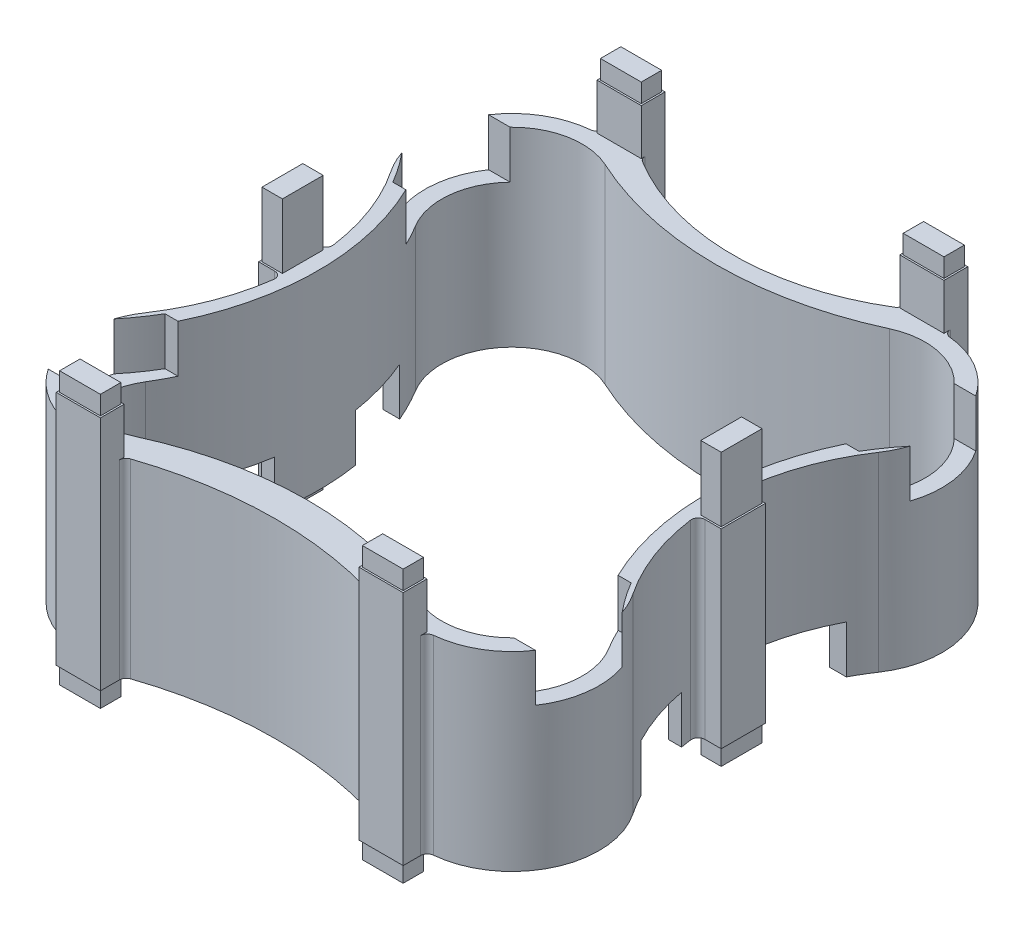
SolidWorks part; units mm, degrees
material "PA 类型 6"
ref_plane "前视基准面" through (0, 0, 0) normal (0, 0, 1) x (1, 0, 0)
ref_plane "上视基准面" through (0, 0, 0) normal (0, 1, 0) x (1, 0, 0)
ref_plane "右视基准面" through (0, 0, 0) normal (1, 0, 0) x (0, 0, -1)
sketch "参考面" plane through (0, 0, 0) normal (0, 1, 0) x (1, 0, 0)
  line L9 (-126.3139, 0) -> (116.7252, 0) construction
  line L10 (121.4406, 121.4406) -> (-121.4406, -121.4406) construction
  line L19 (-81.1154, 0) -> (102.0168, 0) construction
  line L20 (-108.2303, 108.2303) -> (124.7404, -124.7404) construction
  line L37 (0, 0) -> (86.2111, -62.636) construction
  line L56 (0, 63.4476) -> (0, -83.7805) construction
  line L92 (67.1165, -56.1685) -> (56.6027, -48.5298)
  line L94 (74.1596, -46.4745) -> (63.6458, -38.8359)
  line L111 (14.4084, 23.7665) -> (0, 9.3581)
  line L112 (21.4, 67.209) -> (28.6, 67.209)
  line L121 (4.0949, -56.1675) -> (4.0949, -53.2193)
  line L122 (-3.5956, -56.6668) -> (3.5956, -56.6668)
  line L123 (3.5956, -40.6902) -> (-3.5938, -40.6902)
  line L124 (4.0949, -41.1895) -> (4.0949, -44.1377)
  line L125 (-4.0949, -56.1675) -> (-4.0949, -53.2179)
  line L126 (-4.0949, -44.1363) -> (-4.0949, -41.1876)
  line L127 (-4.5418, -52.8684) -> (-4.4444, -52.8684)
  line L128 (-8.5359, -48.8743) -> (-8.5359, -48.4799)
  line L129 (8.5359, -48.8757) -> (8.5359, -48.4813)
  line L130 (4.4444, -52.8698) -> (4.5418, -52.8698)
  line L131 (4.5418, -44.4872) -> (4.4444, -44.4872)
  line L132 (-4.5418, -44.4858) -> (-4.4444, -44.4858)
  line L180 (-67.1165, 56.1685) -> (-56.6027, 48.5298)
  line L181 (-74.1596, 46.4745) -> (-63.6458, 38.8359)
  line L182 (-74.1596, -46.4745) -> (-63.6458, -38.8359)
  line L183 (-67.1165, -56.1685) -> (-56.6027, -48.5298)
  line L194 (-18.9731, -62.4083) -> (18.9712, -62.4083) construction
  line L200 (-11.2634, 52.145) -> (-6.2707, 52.145) construction
  line L201 (-11.2634, 50.8469) -> (-6.2707, 50.8469)
  line L202 (-11.2634, 53.4431) -> (-6.2707, 53.4431)
  line L206 (5.7117, 52.145) -> (0.719, 52.145) construction
  line L207 (5.7117, 53.4431) -> (0.719, 53.4431)
  line L208 (5.7117, 50.8469) -> (0.719, 50.8469)
  line L209 (74.1596, 46.4745) -> (63.6458, 38.8359)
  line L210 (43.9796, 31.9531) -> (60.1362, 43.6915) construction
  line L211 (67.1165, 56.1685) -> (56.6027, 48.5298)
  line L213 (-23.7665, 14.4084) -> (-9.3581, 0)
  line L214 (-58.8004, 0) -> (57.5251, 0) construction
  line L215 (-23.7665, -14.4084) -> (-9.3581, 0)
  line L241 (20.9, 49.291) -> (20.9, 66.709)
  line L242 (21.4, 48.791) -> (28.6, 48.791)
  line L243 (-14.4084, 23.7665) -> (0, 9.3581)
  line L244 (20.9, 58) -> (35.2287, 58) construction
  line L245 (25, 67.209) -> (25, 48.791) construction
  line L246 (29.1, 66.709) -> (29.1, 49.291)
  line L247 (23.7665, -14.4084) -> (9.3581, 0)
  line L248 (23.7665, 14.4084) -> (9.3581, 0)
  line L249 (-14.4084, -23.7665) -> (0, -9.3581)
  line L250 (14.4084, -23.7665) -> (0, -9.3581)
  line L255 (25.5, -41.5) -> (19, -41.5)
  line L256 (-25.5, 41.5) -> (-19, 41.5)
  line L257 (-25.5, 41.5) -> (-25.5, 38)
  line L258 (-25.5, 38) -> (-19, 38)
  line L259 (-19, 41.5) -> (-19, 38)
  line L260 (-34, 3.25) -> (-30.5, 3.25)
  line L261 (-34, 3.25) -> (-34, -3.25)
  line L262 (-34, -3.25) -> (-30.5, -3.25)
  line L263 (-30.5, 3.25) -> (-30.5, -3.25)
  line L264 (-25.5, -38) -> (-19, -38)
  line L265 (-25.5, -38) -> (-25.5, -41.5)
  line L266 (-25.5, -41.5) -> (-19, -41.5)
  line L267 (-19, -38) -> (-19, -41.5)
  line L268 (19, -38) -> (19, -41.5)
  line L269 (25.5, -38) -> (19, -38)
  line L270 (25.5, -38) -> (25.5, -41.5)
  line L271 (34, -3.25) -> (30.5, -3.25)
  line L272 (30.5, 3.25) -> (30.5, -3.25)
  line L273 (34, 3.25) -> (30.5, 3.25)
  line L274 (34, 3.25) -> (34, -3.25)
  line L275 (25.5, 38) -> (19, 38)
  line L276 (19, 41.5) -> (19, 38)
  line L277 (25.5, 41.5) -> (25.5, 38)
  line L278 (25.5, 41.5) -> (19, 41.5)
  circle A40 centre (9.9853, 9.9853) radius 1.0734
  circle A65 centre (12.7313, 12.7313) radius 1.0734
  circle A66 centre (15.2276, 15.2276) radius 1.5477
  circle A67 centre (-15.2276, 15.2276) radius 1.5477
  circle A68 centre (-12.7313, 12.7313) radius 1.0734
  circle A69 centre (-9.9853, 9.9853) radius 1.0734
  circle A70 centre (-9.9853, -9.9853) radius 1.0734
  circle A71 centre (-12.7313, -12.7313) radius 1.0734
  circle A72 centre (-15.2276, -15.2276) radius 1.5477
  circle A82 centre (15.2276, -15.2276) radius 1.5477
  circle A83 centre (12.7313, -12.7313) radius 1.0734
  circle A84 centre (9.9853, -9.9853) radius 1.0734
  circle A85 centre (27.9589, -27.9589) radius 3.1454
  circle A86 centre (-27.9589, -27.9589) radius 3.1454
  circle A101 centre (-27.9589, 27.9589) radius 3.1454
  circle A102 centre (27.9589, 27.9589) radius 3.1454
  circle A104 centre (43.9796, -31.9531) radius 1.5477
  circle A105 centre (60.1362, -43.6915) radius 1.5477
  circle A106 centre (-60.1362, -43.6915) radius 1.5477
  circle A113 centre (-23.2458, 52.145) radius 1.2981
  circle A114 centre (-43.9796, -31.9531) radius 1.5477
  circle A115 centre (60.1362, 43.6915) radius 1.5477
  circle A116 centre (43.9796, 31.9531) radius 1.5477
  circle A117 centre (-43.9796, 31.9531) radius 1.5477
  circle A118 centre (-60.1362, 43.6915) radius 1.5477
  arc A120 (67.1165, -56.1685) -> (74.1596, -46.4745) centre (70.638, -51.3215) ccw
  arc A121 (27.2174, -63.5024) -> (56.6027, -48.5298) centre (45.7245, -63.5024) cw
  arc A128 (-4.0949, -56.1675) -> (-3.5956, -56.6668) centre (-4.0949, -56.6668) ccw
  arc A129 (4.0949, -56.1675) -> (3.5956, -56.6668) centre (4.0949, -56.6668) cw
  arc A130 (4.0949, -41.1895) -> (3.5956, -40.6902) centre (4.0949, -40.6902) ccw
  arc A131 (-4.0949, -41.1876) -> (-3.5938, -40.6902) centre (-4.0931, -40.6884) cw
  arc A132 (8.5359, -48.4813) -> (4.5418, -44.4872) centre (4.5418, -48.4813) ccw
  arc A133 (-4.5418, -44.4858) -> (-8.5359, -48.4799) centre (-4.5418, -48.4799) ccw
  arc A134 (-4.5418, -52.8684) -> (-8.5359, -48.8743) centre (-4.5418, -48.8743) cw
  arc A135 (8.5359, -48.8757) -> (4.5418, -52.8698) centre (4.5418, -48.8757) cw
  arc A136 (4.0949, -44.1377) -> (4.4444, -44.4872) centre (4.4444, -44.1377) ccw
  arc A137 (4.0949, -53.2193) -> (4.4444, -52.8698) centre (4.4444, -53.2193) cw
  arc A138 (-4.0949, -44.1363) -> (-4.4444, -44.4858) centre (-4.4444, -44.1363) cw
  arc A139 (-4.0949, -53.2179) -> (-4.4444, -52.8684) centre (-4.4444, -53.2179) ccw
  arc A165 (-11.2634, 50.8469) -> (-11.2634, 53.4431) centre (-11.2634, 52.145) cw
  arc A166 (-6.2707, 53.4431) -> (-6.2707, 50.8469) centre (-6.2707, 52.145) cw
  arc A169 (5.7117, 53.4431) -> (5.7117, 50.8469) centre (5.7117, 52.145) cw
  arc A170 (0.719, 50.8469) -> (0.719, 53.4431) centre (0.719, 52.145) cw
  circle A175 centre (0, -38.4435) radius 1.5477
  circle A176 centre (0, -58.9135) radius 1.5477
  arc A177 (67.1165, 56.1685) -> (74.1596, 46.4745) centre (70.638, 51.3215) cw
  arc A178 (63.6458, 38.8359) -> (63.6458, -38.8359) centre (91.8617, 0) ccw
  circle A179 centre (43.9796, -31.9531) radius 5.9912 construction
  arc A180 (35.3497, 58.9683) -> (56.6027, 48.5298) centre (48.7329, 59.3617) ccw
  arc A181 (-67.1165, 56.1685) -> (-74.1596, 46.4745) centre (-70.638, 51.3215) ccw
  arc A182 (-35.3497, 58.9683) -> (-56.6027, 48.5298) centre (-48.7329, 59.3617) cw
  arc A183 (-63.6458, 38.8359) -> (-63.6458, -38.8359) centre (-91.8617, 0) cw
  arc A184 (-67.1165, -56.1685) -> (-74.1596, -46.4745) centre (-70.638, -51.3215) cw
  arc A185 (-27.2174, -63.5024) -> (-56.6027, -48.5298) centre (-45.7245, -63.5024) ccw
  arc A190 (-23.7665, 14.4084) -> (-29.7764, 19.3723) centre (-52.8107, -14.6358) ccw
  arc A191 (-23.7665, -14.4084) -> (-29.7764, -19.3723) centre (-52.8107, 14.6358) cw
  arc A192 (-29.7764, -19.3723) -> (-29.7764, 19.3723) centre (-91.8617, 0) ccw
  circle A202 centre (25, 69.659) radius 1.05
  arc A203 (20.9, 66.709) -> (21.4, 67.209) centre (20.9, 67.209) cw
  arc A204 (20.9, 49.291) -> (21.4, 48.791) centre (20.9, 48.791) ccw
  circle A205 centre (25, 46.341) radius 1.05
  arc A206 (29.1, 66.709) -> (28.6, 67.209) centre (29.1, 67.209) ccw
  arc A207 (29.1, 49.291) -> (28.6, 48.791) centre (29.1, 48.791) cw
  arc A208 (-14.4084, 23.7665) -> (-19.3723, 29.7764) centre (14.6358, 52.8107) cw
  arc A209 (-19.3723, 29.7764) -> (19.3723, 29.7764) centre (0, 91.8617) ccw
  arc A210 (14.4084, 23.7665) -> (19.3723, 29.7764) centre (-14.6358, 52.8107) ccw
  arc A211 (23.7665, 14.4084) -> (29.7764, 19.3723) centre (52.8107, -14.6358) cw
  arc A212 (29.7764, 19.3723) -> (29.7764, -19.3723) centre (91.8617, 0) ccw
  arc A213 (23.7665, -14.4084) -> (29.7764, -19.3723) centre (52.8107, 14.6358) ccw
  arc A214 (14.4084, -23.7665) -> (19.3723, -29.7764) centre (-14.6358, -52.8107) cw
  arc A215 (19.3723, -29.7764) -> (-19.3723, -29.7764) centre (0, -91.8617) ccw
  arc A216 (-14.4084, -23.7665) -> (-19.3723, -29.7764) centre (14.6358, -52.8107) ccw
  point P77 (0, 0)
  point P112 (-8.7671, 52.145)
  point P168 (3.2153, 52.145)
  point P443 (0, 0)
  dimension "D1" = 4
  dimension "D3" = 58
  dimension "D5" = 8.2
  dimension "D2" = 0.5
  dimension "D4" = 2.45
  dimension "D6" = 7.2
  dimension "D7" = 25
  dimension "D8" = 19
  dimension "D9" = 30.5
  dimension "D14" = 6.5
  dimension "D15" = 3.5
  dimension "D16" = 38
  dimension "D17" = 38
sketch "草图2" plane through (0, 0, 0) normal (0, 1, 0) x (1, 0, 0)
  line L1 (-61.3007, 0) -> (77.257, 0) construction
  line L8 (-30.5, 3.25) -> (-34, 3.25)
  line L9 (-34, 3.25) -> (-34, -3.25)
  line L31 (-34, -3.25) -> (-30.5, -3.25)
  line L33 (-25.5, 38) -> (-25.5, 41.5)
  line L56 (-25.5, 41.5) -> (-19, 41.5)
  line L57 (-19, 41.5) -> (-19, 38)
  line L58 (-25.5, -38) -> (-25.5, -41.5)
  line L59 (-25.5, -41.5) -> (-19, -41.5)
  line L60 (-19, -41.5) -> (-19, -38)
  line L61 (19, -41.5) -> (19, -38)
  line L62 (25.5, -41.5) -> (19, -41.5)
  line L63 (25.5, -38) -> (25.5, -41.5)
  line L64 (19, 41.5) -> (19, 38)
  line L65 (25.5, 41.5) -> (19, 41.5)
  line L66 (25.5, 38) -> (25.5, 41.5)
  line L67 (34, -3.25) -> (30.5, -3.25)
  line L68 (34, 3.25) -> (34, -3.25)
  line L69 (30.5, 3.25) -> (34, 3.25)
  line L74 (-126.3139, 0) -> (116.7252, 0) construction
  line L75 (0, 68.5797) -> (0, -68.5797) construction
  line L76 (0, 63.4476) -> (0, -83.7805) construction
  line L77 (-108.2303, 108.2303) -> (124.7404, -124.7404) construction
  arc A49 (-25.5, 38) -> (-35.8347, 18.0724) centre (-25.2016, 25.2016) ccw
  arc A52 (-20.8758, 34.5817) -> (-34.0392, 19.854) centre (-25.2016, 25.2016) ccw
  arc A53 (-34.0392, -19.854) -> (-34.0392, 19.854) centre (-66.8509, 0) ccw
  arc A55 (-35.8347, -18.0724) -> (-30.5, -3.25) centre (-62.7894, 0) ccw
  arc A56 (-25.5, -38) -> (-35.8347, -18.0724) centre (-25.2016, -25.2016) cw
  arc A57 (-20.8758, -34.5817) -> (-34.0392, -19.854) centre (-25.2016, -25.2016) cw
  arc A59 (-30.5, 3.25) -> (-35.8347, 18.0724) centre (-62.7894, 0) ccw
  arc A62 (30.5, 3.25) -> (35.8347, 18.0724) centre (62.7894, 0) cw
  arc A65 (20.8758, -34.5817) -> (34.0392, -19.854) centre (25.2016, -25.2016) ccw
  arc A66 (25.5, -38) -> (35.8347, -18.0724) centre (25.2016, -25.2016) ccw
  arc A69 (35.8347, -18.0724) -> (30.5, -3.25) centre (62.7894, 0) cw
  arc A70 (34.0392, -19.854) -> (34.0392, 19.854) centre (66.8509, 0) cw
  arc A71 (20.8758, 34.5817) -> (34.0392, 19.854) centre (25.2016, 25.2016) cw
  arc A72 (25.5, 38) -> (35.8347, 18.0724) centre (25.2016, 25.2016) cw
  arc A73 (-19, 38) -> (19, 38) centre (0, 67.9818) ccw
  arc A74 (-20.8758, 34.5817) -> (20.8758, 34.5817) centre (0, 79.8492) ccw
  arc A75 (-19, -38) -> (19, -38) centre (0, -91.6977) cw
  arc A76 (-20.8758, -34.5817) -> (20.8758, -34.5817) centre (0, -79.8492) cw
  point P33 (-28.5, 0)
  point P34 (28.5, 0)
  point P37 (0, 30)
  point P38 (0, -30)
  point P44 (-36.5661, 31.0954)
  point P54 (0, 32.4866)
  dimension "D1" = 2
  dimension "D3" = 60
  dimension "D5" = 2.4866
  dimension "D2" = 57
  dimension "D4" = 48
extrude "主结构-28mm-铝柱补偿7mm" add sketch "草图2" against normal blind 28
sketch "草图9" plane through (0, 0, 0) normal (0, 1, 0) x (1, 0, 0)
  line L0 (-25.5, 41.5) -> (-19, 41.5)
  line L1 (-19, 41.5) -> (-19, 38)
  line L2 (-19, 38) -> (-25.5, 38)
  line L3 (-25.5, 38) -> (-25.5, 41.5)
  line L4 (-34, 3.25) -> (-30.5, 3.25)
  line L5 (-30.5, 3.25) -> (-30.5, -3.25)
  line L6 (-30.5, -3.25) -> (-34, -3.25)
  line L7 (-34, -3.25) -> (-34, 3.25)
  line L8 (-25.5, -38) -> (-19, -38)
  line L9 (-19, -38) -> (-19, -41.5)
  line L10 (-19, -41.5) -> (-25.5, -41.5)
  line L11 (-25.5, -41.5) -> (-25.5, -38)
  line L12 (0, 0) -> (0, 49.4307) construction
  line L13 (25.5, -41.5) -> (25.5, -38)
  line L14 (19, -41.5) -> (25.5, -41.5)
  line L15 (19, -38) -> (19, -41.5)
  line L16 (25.5, -38) -> (19, -38)
  line L17 (34, -3.25) -> (34, 3.25)
  line L18 (30.5, -3.25) -> (34, -3.25)
  line L19 (30.5, 3.25) -> (30.5, -3.25)
  line L20 (34, 3.25) -> (30.5, 3.25)
  line L21 (25.5, 38) -> (25.5, 41.5)
  line L22 (19, 38) -> (25.5, 38)
  line L23 (19, 41.5) -> (19, 38)
  line L24 (25.5, 41.5) -> (19, 41.5)
  line M16 (-25.5, -38) -> (-25.5, -41.5)
  line M17 (-25.5, -41.5) -> (-19, -41.5)
  line M18 (-19, -41.5) -> (-19, -38)
  line M20 (19, -38) -> (19, -41.5)
  line M21 (19, -41.5) -> (25.5, -41.5)
  line M22 (25.5, -41.5) -> (25.5, -38)
  line M30 (25.5, 38) -> (25.5, 41.5)
  line M31 (25.5, 41.5) -> (19, 41.5)
  line M32 (19, 41.5) -> (19, 38)
  line M34 (-19, 38) -> (-19, 41.5)
  line M35 (-19, 41.5) -> (-25.5, 41.5)
  line M36 (-25.5, 41.5) -> (-25.5, 38)
extrude "上板支撑" add sketch "草图9" along normal blind 6.75 contours L2 M34 M35 M36 | L22 M32 M30 M31 | L8 M16 M17 M18 | L16 M22 M20 M21 region at (-22.25, 0, -39.75) region at (-22.25, 0, 39.75) region at (22.25, 0, 39.75) region at (22.25, 0, -39.75)
sketch "草图5" plane through (0, 0, 0) normal (0, 1, 0) x (1, 0, 0)
  line L0 (-68.648, 0) -> (77.219, 0) construction
  line L1 (-126.3139, 0) -> (116.7252, 0) construction
  line L2 (0, 57.3258) -> (0, -69.9488) construction
  line L3 (0, 63.4476) -> (0, -83.7805) construction
  line L4 (-34, 3.25) -> (-30.5, 3.25) construction
  line L5 (-33.75, 3) -> (-30.75, 3)
  line L6 (-33.75, 3) -> (-33.75, -3)
  line L7 (-33.75, -3) -> (-30.75, -3)
  line L8 (-30.75, 3) -> (-30.75, -3)
  line L9 (-34, 3.25) -> (-34, -3.25) construction
  line L10 (-19, -38) -> (-19, -41.5) construction
  line L11 (-25.25, -38.25) -> (-19.25, -38.25)
  line L12 (-25.25, -38.25) -> (-25.25, -41.25)
  line L13 (-25.25, -41.25) -> (-19.25, -41.25)
  line L14 (-19.25, -38.25) -> (-19.25, -41.25)
  line L15 (-25.5, -41.5) -> (-19, -41.5) construction
  line L16 (-25.25, 41.25) -> (-19.25, 41.25)
  line L17 (-19.25, 38.25) -> (-19.25, 41.25)
  line L18 (-25.25, 38.25) -> (-19.25, 38.25)
  line L19 (-25.25, 38.25) -> (-25.25, 41.25)
  line L20 (25.25, 38.25) -> (25.25, 41.25)
  line L21 (25.25, 38.25) -> (19.25, 38.25)
  line L22 (19.25, 38.25) -> (19.25, 41.25)
  line L23 (25.25, 41.25) -> (19.25, 41.25)
  line L24 (19.25, -38.25) -> (19.25, -41.25)
  line L25 (25.25, -41.25) -> (19.25, -41.25)
  line L26 (25.25, -38.25) -> (25.25, -41.25)
  line L27 (25.25, -38.25) -> (19.25, -38.25)
  line L28 (30.75, 3) -> (30.75, -3)
  line L29 (33.75, -3) -> (30.75, -3)
  line L30 (33.75, 3) -> (33.75, -3)
  line L31 (33.75, 3) -> (30.75, 3)
  dimension "D1" = 0.25
  dimension "D2" = 0.25
  dimension "D3" = 3
  dimension "D4" = 0.25
  dimension "D5" = 0.25
extrude "凸台-拉伸3" add sketch "草图5" along normal blind 9.5 contours L19 L18 L17 L16 | L20 L23 L22 L21 | L8 L5 L6 L7 | L26 L27 L24 L25 | L14 L11 L12 L13 | L30 L29 L28 L31 region at (-32.25, 0, 0) region at (-22.25, 0, 39.75) region at (-22.25, 0, -39.75) region at (22.25, 0, -39.75) region at (22.25, 0, 39.75)
sketch "草图6" plane through (0, -28, 0) normal (0, -1, 0) x (1, 0, 0)
  line L0 (-44.389, 0) -> (42.3877, 0) construction
  line L1 (0, 51.2716) -> (0, -51.2716) construction
  line L2 (-25.25, 41.25) -> (-19.25, 41.25)
  line L3 (-33.75, 3) -> (-30.75, 3)
  line L4 (-33.75, 3) -> (-33.75, -3)
  line L5 (-33.75, -3) -> (-30.75, -3)
  line L6 (-30.75, 3) -> (-30.75, -3)
  line L7 (-25.25, -38.25) -> (-19.25, -38.25)
  line L8 (-25.25, -38.25) -> (-25.25, -41.25)
  line L9 (-25.25, -41.25) -> (-19.25, -41.25)
  line L10 (-19.25, -38.25) -> (-19.25, -41.25)
  line L11 (-19.25, 38.25) -> (-19.25, 41.25)
  line L12 (-25.25, 38.25) -> (-19.25, 38.25)
  line L13 (-25.25, 38.25) -> (-25.25, 41.25)
  line L14 (25.25, 38.25) -> (25.25, 41.25)
  line L15 (25.25, 38.25) -> (19.25, 38.25)
  line L16 (19.25, 38.25) -> (19.25, 41.25)
  line L17 (19.25, -38.25) -> (19.25, -41.25)
  line L18 (25.25, -41.25) -> (19.25, -41.25)
  line L19 (25.25, -38.25) -> (25.25, -41.25)
  line L20 (25.25, -38.25) -> (19.25, -38.25)
  line L21 (30.75, 3) -> (30.75, -3)
  line L22 (33.75, -3) -> (30.75, -3)
  line L23 (33.75, 3) -> (33.75, -3)
  line L24 (33.75, 3) -> (30.75, 3)
  line L25 (25.25, 41.25) -> (19.25, 41.25)
  line L26 (-34, 3.25) -> (-30.5, 3.25) construction
  line L27 (-34, -3.25) -> (-34, 3.25) construction
  line L28 (-25.5, -41.5) -> (-25.5, -38) construction
  line L29 (-19, -41.5) -> (-25.5, -41.5) construction
  dimension "D1" = 0.25
  dimension "D2" = 0.25
  dimension "D3" = 0.25
  dimension "D4" = 0.25
  dimension "D5" = 3
extrude "凸台-拉伸4" add sketch "草图6" along normal blind 2.5
fillet "圆角1" radius 1 12 edges at (30.5, -14, -3.25) (25.5, -14, -38) (-19, -14, -38) (19, -14, -38) (-25.5, -14, -38) (-30.5, -14, -3.25) (19, -14, 38) (30.5, -14, 3.25) (25.5, -14, 38) (-19, -14, 38) (-25.5, -14, 38) (-30.5, -14, 3.25)
sketch "草图7" plane through (0, 0, 0) normal (0, 1, 0) x (1, 0, 0)
  line L0 (-43.0337, 0) -> (42.851, 0) construction
  line L1 (0, 36.718) -> (0, -44.8375) construction
  line L2 (0, 0) -> (-41.2356, -29.9594) construction
  line L3 (-34.2586, -16.7459) -> (-32.3492, -16.7459)
  line L4 (-35.8097, -32.3679) -> (-32.6409, -32.3679)
  line L5 (34.2586, -16.7459) -> (32.3492, -16.7459)
  line L6 (35.8097, -32.3679) -> (32.6409, -32.3679)
  line L8 (-34.2586, 16.7459) -> (-32.3492, 16.7459)
  line L9 (-35.8097, 32.3679) -> (-32.6409, 32.3679)
  line L10 (35.8097, 32.3679) -> (32.6409, 32.3679)
  line L11 (34.2586, 16.7459) -> (32.3492, 16.7459)
  arc A0 (-34.0392, -19.854) -> (-32.6409, -32.3679) centre (-25.2016, -25.2016) ccw
  arc A1 (-37.3416, -21.1387) -> (-35.8097, -32.3679) centre (-25.2016, -25.2016) ccw
  arc A2 (-37.3416, -21.1387) -> (-34.2586, -16.7459) centre (-62.7894, 0) ccw
  arc A3 (-34.0392, -19.854) -> (-32.3492, -16.7459) centre (-66.8509, 0) ccw
  arc A4 (34.0392, -19.854) -> (32.3492, -16.7459) centre (66.8509, 0) cw
  arc A5 (37.3416, -21.1387) -> (34.2586, -16.7459) centre (62.7894, 0) cw
  arc A6 (37.3416, -21.1387) -> (35.8097, -32.3679) centre (25.2016, -25.2016) cw
  arc A7 (34.0392, -19.854) -> (32.6409, -32.3679) centre (25.2016, -25.2016) cw
  arc A12 (-34.0392, 19.854) -> (-32.3492, 16.7459) centre (-66.8509, 0) cw
  arc A13 (-37.3416, 21.1387) -> (-34.2586, 16.7459) centre (-62.7894, 0) cw
  arc A14 (-37.3416, 21.1387) -> (-35.8097, 32.3679) centre (-25.2016, 25.2016) cw
  arc A15 (-34.0392, -19.854) -> (-34.0392, 19.854) centre (-66.8509, 0) ccw construction
  arc A16 (-34.0392, 19.854) -> (-32.6409, 32.3679) centre (-25.2016, 25.2016) cw
  arc A17 (34.0392, 19.854) -> (32.6409, 32.3679) centre (25.2016, 25.2016) ccw
  arc A18 (37.3416, 21.1387) -> (35.8097, 32.3679) centre (25.2016, 25.2016) ccw
  arc A19 (37.3416, 21.1387) -> (34.2586, 16.7459) centre (62.7894, 0) ccw
  arc A20 (34.0392, 19.854) -> (32.3492, 16.7459) centre (66.8509, 0) ccw
  arc A21 (-20.8758, 34.5817) -> (-34.0392, 19.854) centre (-25.2016, 25.2016) ccw construction
  arc A22 (-34.0392, -19.854) -> (-20.8758, -34.5817) centre (-25.2016, -25.2016) ccw construction
  arc A23 (35.8347, 18.0724) -> (26.4059, 37.9467) centre (25.2016, 25.2016) ccw construction
  arc A24 (-26.4059, 37.9467) -> (-35.8347, 18.0724) centre (-25.2016, 25.2016) ccw construction
  point P50 (0, 0)
  point P51 (0, 0)
  point P55 (0, 0)
  dimension "D1" = 36
extrude "电调过线" cut sketch "草图7" against normal blind 7
sketch "草图8" plane through (0, -28, 0) normal (0, -1, 0) x (1, 0, 0)
  line L0 (-48.2566, 0) -> (46.2095, 0) construction
  line L1 (0, 0) -> (0, -36.4146) construction
  line L2 (-30.8873, -5.9516) -> (-28.9646, -5.9516)
  line L3 (-34.0577, -15.0884) -> (-31.5928, -15.0884)
  line L4 (-34.0577, 15.0884) -> (-31.5928, 15.0884)
  line L5 (-30.8873, 5.9516) -> (-28.9646, 5.9516)
  line L6 (30.8873, -5.9516) -> (28.9646, -5.9516)
  line L7 (34.0577, -15.0884) -> (31.5928, -15.0884)
  line L8 (30.8873, 5.9516) -> (28.9646, 5.9516)
  line L9 (34.0577, 15.0884) -> (31.5928, 15.0884)
  arc A0 (-35.8347, -18.0724) -> (-30.6345, -4.3851) centre (-62.7894, 0) ccw construction
  arc A1 (-34.0392, -19.854) -> (-34.0392, 19.854) centre (-66.8509, 0) ccw construction
  arc A2 (-30.8873, -5.9516) -> (-34.0577, -15.0884) centre (-62.7894, 0) cw
  arc A3 (-28.9646, -5.9516) -> (-31.5928, -15.0884) centre (-66.8509, 0) cw
  arc A4 (-30.8873, 5.9516) -> (-34.0577, 15.0884) centre (-62.7894, 0) ccw
  arc A5 (-28.9646, 5.9516) -> (-31.5928, 15.0884) centre (-66.8509, 0) ccw
  arc A6 (30.8873, -5.9516) -> (34.0577, -15.0884) centre (62.7894, 0) ccw
  arc A7 (28.9646, -5.9516) -> (31.5928, -15.0884) centre (66.8509, 0) ccw
  arc A8 (28.9646, 5.9516) -> (31.5928, 15.0884) centre (66.8509, 0) cw
  arc A9 (30.8873, 5.9516) -> (34.0577, 15.0884) centre (62.7894, 0) cw
extrude "电源过线" cut sketch "草图8" against normal blind 7
